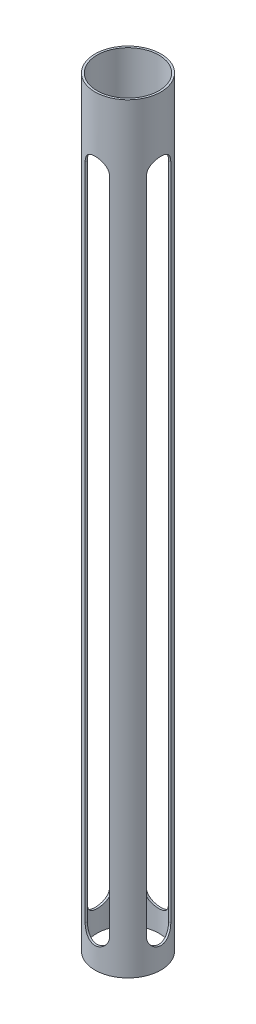
SolidWorks part; units mm, degrees
material "7075-T6 (SN)"
ref_plane "Front Plane" through (0, 0, 0) normal (0, 0, 1) x (1, 0, 0)
ref_plane "Top Plane" through (0, 0, 0) normal (0, 1, 0) x (1, 0, 0)
ref_plane "Right Plane" through (0, 0, 0) normal (1, 0, 0) x (0, 0, -1)
sketch "Sketch1" plane through (0, 0, 0) normal (0, 1, 0) x (1, 0, 0)
  circle A0 centre (0, 0) radius 32.5
  circle A1 centre (0, 0) radius 30.5
extrude "Boss-Extrude1" add sketch "Sketch1" along normal blind 750
sketch "Sketch2" plane through (0, 0, 0) normal (0, 0, 1) x (1, 0, 0)
  line L0 (0, 480) -> (0, 428.756) construction
  line L2 (0, 683.0807) -> (0, 33.0807) construction
  line L3 (12, 683.0807) -> (12, 33.0807)
  line L4 (-12, 683.0807) -> (-12, 33.0807)
  arc A0 (12, 683.0807) -> (-12, 683.0807) centre (0, 683.0807) ccw
  arc A1 (-12, 33.0807) -> (12, 33.0807) centre (0, 33.0807) ccw
  point P3 (0, 358.0807)
extrude "Cut-Extrude1" cut sketch "Sketch2" against normal mid plane 100
sketch "Sketch5" plane through (0, 0, 0) normal (1, 0, 0) x (0, 0, -1)
  line L0 (0, 683.0807) -> (0, 33.0807) construction
  line L1 (12, 683.0807) -> (12, 33.0807)
  line L2 (-12, 683.0807) -> (-12, 33.0807)
  arc A0 (12, 683.0807) -> (-12, 683.0807) centre (0, 683.0807) ccw
  arc A1 (-12, 33.0807) -> (12, 33.0807) centre (0, 33.0807) ccw
  point P3 (0, 358.0807)
extrude "Cut-Extrude3" cut sketch "Sketch5" against normal mid plane 100
